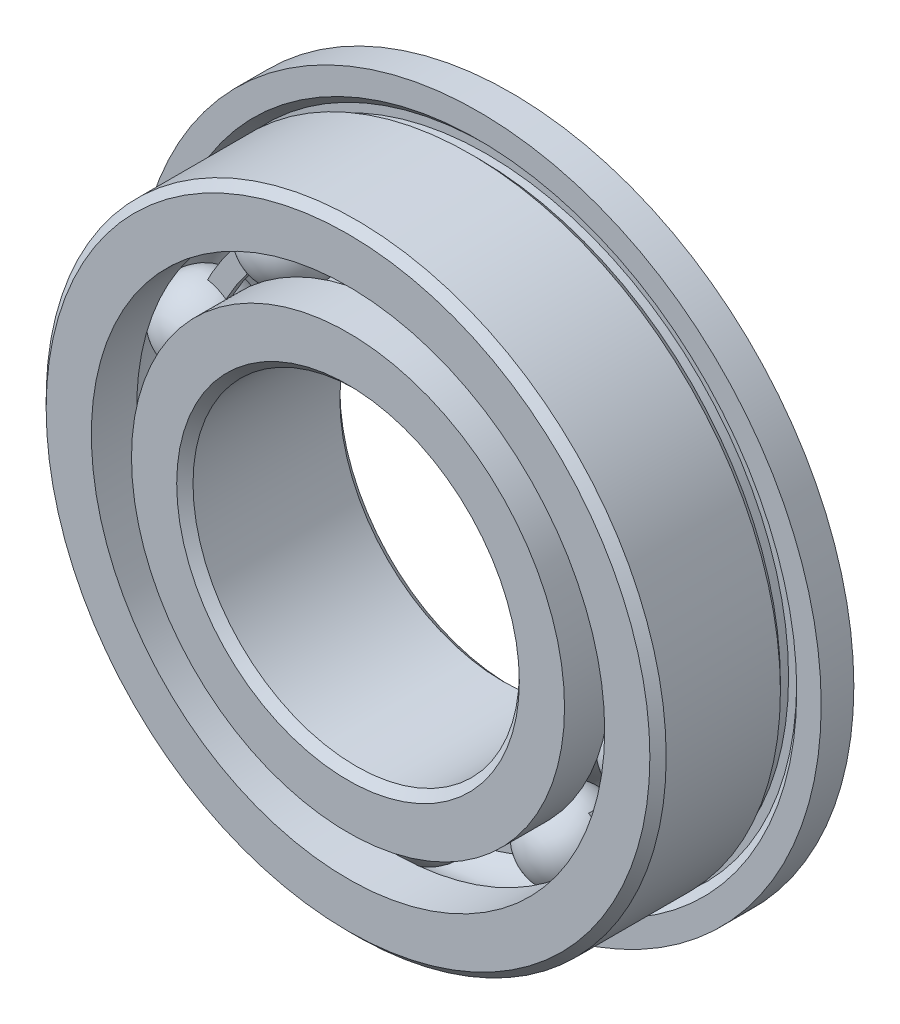
SolidWorks part; units mm, degrees
material "AISI 1045 钢，冷拔"
ref_plane "Front Plane" through (0, 0, 0) normal (0, 0, 1) x (1, 0, 0)
ref_plane "Top Plane" through (0, 0, 0) normal (0, 1, 0) x (1, 0, 0)
ref_plane "Right Plane" through (0, 0, 0) normal (1, 0, 0) x (0, 0, -1)
sketch "Sketch1" plane through (0, 0, 0) normal (1, 0, 0) x (0, 0, -1)
  line L0 (-2.5, 0) -> (2.5, 0) construction
  line L1 (0, 9.5) -> (0, -9.5) construction
  line L2 (2.25, 9.5) -> (-2.25, 9.5) construction
  line L3 (-2.25, 9.5) -> (-2.5, 9.25)
  line L4 (-2.5, 9.25) -> (-2.5, 7.8654)
  line L5 (-2.5, 7.8654) -> (-1.1111, 7.8654)
  line L6 (2.5, 7.8654) -> (1.1111, 7.8654)
  line L7 (2.5, 9.25) -> (2.5, 7.8654)
  line L8 (2.25, 9.5) -> (2.5, 9.25) construction
  line L9 (0, 9.5) -> (0, 7.25) construction
  line L10 (0, 7.25) -> (0, 5) construction
  line L11 (1.5, 0) -> (1.5, 9.5) construction
  line L12 (2.5, 9.25) -> (2.5, 10.5)
  line L13 (2.5, 10.5) -> (1.5, 10.5)
  line L14 (1.5, 10.5) -> (1.5, 9.75)
  line L15 (1.5, 9.75) -> (1.75, 9.5)
  line L16 (1.75, 9.5) -> (1.75, 9.25)
  line L17 (1.75, 9.25) -> (1.5, 9.25)
  line L18 (1.5, 9.25) -> (1.25, 9.5)
  line L19 (-2.25, 9.5) -> (1.25, 9.5)
  line L20 (2.5, 10.5) -> (2.5, -10.5) construction
  line L21 (1.5, 9.5) -> (1.5, 9.75) construction
  line L22 (1.5, 9.5) -> (1.25, 9.5) construction
  arc A0 (-1.1111, 7.8654) -> (1.1111, 7.8654) centre (0, 7.25) cw
  point P14 (0, 5)
  point P15 (1.5, 0)
  point P25 (2.5, 0)
  dimension "Width" = 5
  dimension "OD" = 19
  dimension "D1" = 45
  dimension "D2" = 0.25
  dimension "ID" = 10
  dimension "D3" = 2.2222
  dimension "D4" = 0.6154
  dimension "Th" = 1
  dimension "Flange OD" = 21
revolve "Revolve1" add sketch "Sketch1" angle 360 about L0
sketch "Sketch3" plane through (0, 0, 0) normal (1, 0, 0) x (0, 0, -1)
  line L0 (-2.5, 6.6346) -> (-1.1111, 6.6346)
  line L1 (0, 9.5) -> (0, -9.5) construction
  line L2 (-2.5, 9.25) -> (-2.5, 7.8654) construction
  line L3 (-2.5, 6.6346) -> (-2.5, 5.25)
  line L4 (-2.25, 9.5) -> (-2.5, 9.25) construction
  line L5 (-2.5, 5.25) -> (-2.25, 5)
  line L6 (-2.25, 5) -> (2.25, 5)
  line L8 (2.25, 5) -> (2.5, 5.25)
  line L10 (2.5, 5.25) -> (2.5, 6.6346)
  line L11 (2.5, 6.6346) -> (1.1111, 6.6346)
  line L13 (2.25, 9.5) -> (2.5, 9.25) construction
  arc A0 (1.1111, 7.8654) -> (-1.1111, 7.8654) centre (0, 7.25) ccw construction
  arc A1 (1.1111, 6.6346) -> (-1.1111, 6.6346) centre (0, 7.25) cw
revolve "Revolve3" add sketch "Sketch3" angle 360 about L0
sketch "Sketch6" plane through (0, 0, 0) normal (1, 0, 0) x (0, 0, -1)
  line L1 (-0.1026, 7.5577) -> (0.1026, 7.5577)
  line L2 (-0.1026, 7.5577) -> (-0.1026, 6.9423)
  line L3 (-0.1026, 6.9423) -> (0.1026, 6.9423)
  line L4 (0.1026, 7.5577) -> (0.1026, 6.9423)
  line L5 (-0.1026, 7.5577) -> (0.1026, 6.9423) construction
  line L6 (-0.1026, 6.9423) -> (0.1026, 7.5577) construction
  point P4 (0, 7.25)
  dimension "D1" = 0.6154
  dimension "D2" = 0.2051
revolve "Revolve6" add sketch "Sketch6" angle 360 about L0
sketch "Sketch4" plane through (0, 0, 0) normal (1, 0, 0) x (0, 0, -1)
  line L0 (-1.2701, 7.25) -> (1.2701, 7.25)
  arc A2 (-1.2701, 7.25) -> (1.2701, 7.25) centre (0, 7.25) cw
  arc A3 (1.1111, 7.8654) -> (-1.1111, 7.8654) centre (0, 7.25) ccw construction
revolve "Revolve4" add sketch "Sketch4" angle 360 about L0
ref_axis "Axis1" through (0, 0, -2.5) along (0, 0, 1)
pattern_circular "CirPattern1" count 10 every 36 about axis through (0, 0, -2.5) along (0, 0, 1) of bodies 104
sketch "Sketch5" plane through (0, 0, 0) normal (1, 0, 0) x (0, 0, -1)
  line L0 (-2.5, 7.8654) -> (-1.1111, 7.8654) construction
  line L1 (-2.375, 7.8654) -> (-1.2701, 7.8654)
  line L2 (-2.375, 7.8654) -> (-2.375, 6.6346)
  line L3 (-2.375, 6.6346) -> (-1.2701, 6.6346)
  line L4 (-1.2701, 7.8654) -> (-1.2701, 6.6346)
  line L5 (-2.5, 6.6346) -> (-1.1111, 6.6346) construction
  line L6 (2.5, 7.8654) -> (1.1111, 7.8654) construction
  line L7 (2.375, 7.8654) -> (1.2701, 7.8654)
  line L8 (2.375, 7.8654) -> (2.375, 6.6346)
  line L9 (2.375, 6.6346) -> (1.2701, 6.6346)
  line L10 (1.2701, 7.8654) -> (1.2701, 6.6346)
  line L11 (2.5, 6.6346) -> (1.1111, 6.6346) construction
  line L12 (-2.25, 9.5) -> (-2.5, 9.25) construction
  point P18 (-2.375, 9.375)
revolve "Revolve5" [suppressed] add sketch "Sketch5" angle 360 about L0
ref_axis "Center Axis 1" through (0, 0, -2.25) along (0, 0, 1)
ref_plane "Contact Plane 1" through (0, 0, -2.5) normal (0, 0, -1) x (-1, 0, 0)
ref_plane "Contact Plane 2" through (0, 0, -1.5) normal (0, 0, 1) x (1, 0, 0)
equation "\"D2@Sketch1\" = \"Width@Sketch1\"*.05"
equation "\"D3@Sketch1\" = \"Width@Sketch1\"/2.25"
equation "\"D4@Sketch1\" = (((\"OD@Sketch1\"-\"Width@Sketch1\")/2)/3.25)/3.5"
equation "\"D2@CirPattern1\" = 360/\"Balls@CirPattern1\""
equation "\"D1@Sketch6\"=\"D4@Sketch1\""
equation "\"D2@Sketch6\"=\"D1@Sketch6\"/3"
